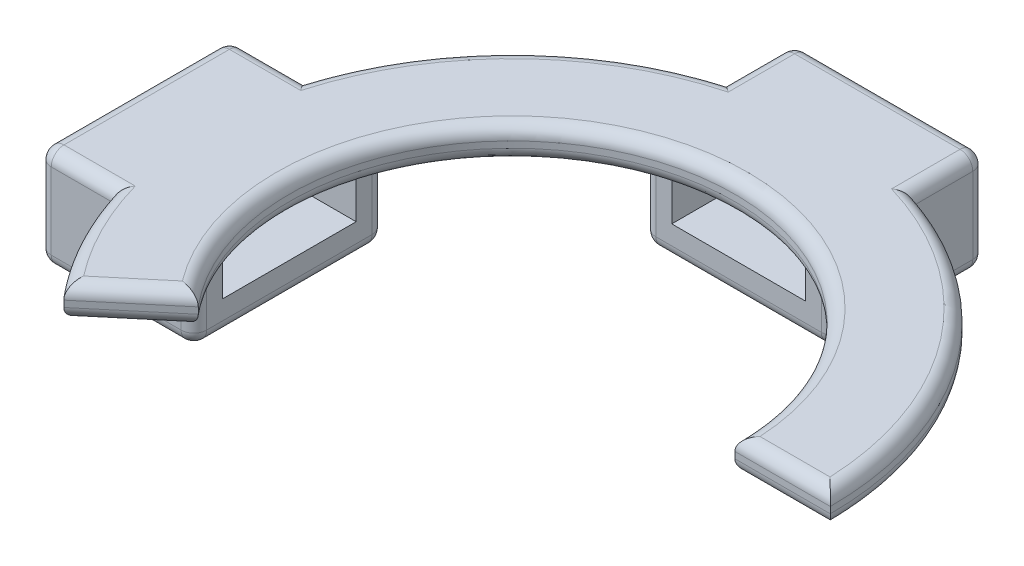
SolidWorks part; units mm, degrees
ref_plane "Front Plane" through (0, 0, 0) normal (0, 0, 1) x (1, 0, 0)
ref_plane "Top Plane" through (0, 0, 0) normal (0, 1, 0) x (1, 0, 0)
ref_plane "Right Plane" through (0, 0, 0) normal (1, 0, 0) x (0, 0, -1)
sketch "Sketch1" plane through (0, 0, 0) normal (0, 1, 0) x (1, 0, 0)
  line L0 (0, -32.004) -> (0, -22.9826) construction
  line L1 (0, 98.8258) -> (0, -27.4933) construction
  line L2 (-77.0851, 0) -> (82.0908, 0) construction
  line L5 (-15, 65) -> (15, 65)
  line L6 (-15, 65) -> (-15, 54.0833)
  line L7 (15, 65) -> (15, 53.7121)
  line L8 (-50.5901, 6.2047) -> (-35.5901, 6.2047)
  line L9 (34.4099, 6.2047) -> (49.4099, 6.2047)
  arc A2 (-50.5901, 6.2047) -> (49.4099, 6.2047) centre (-0.5901, 6.2047) cw
  arc A3 (-15, 54.0833) -> (15, 53.7121) centre (-0.5901, 6.2047) cw
  arc A4 (-35.5901, 6.2047) -> (34.4099, 6.2047) centre (-0.5901, 6.2047) cw
  dimension "D1" = 15
  dimension "D2" = 65
  dimension "D3" = 30
  dimension "D4" = 15
extrude "Boss-Extrude1" add sketch "Sketch1" along normal blind 5 contours L8 A4 L9 A2 | L6 A2 L7 L5 region at (0.0952, 0, -60.1952) region at (0.0147, 0, -55.0829)
sketch "Sketch2" plane through (0, 0, 0) normal (0, 1, 0) x (1, 0, 0)
  line L0 (-38.8923, -25.9347) -> (-27.4017, -16.2928)
  line L1 (-50.5901, 6.2047) -> (-35.5901, 6.2047)
  arc A0 (-35.5901, 6.2047) -> (-27.4017, -16.2928) centre (-0.5901, 6.2047) ccw
  arc A1 (-50.5901, 6.2047) -> (-38.8923, -25.9347) centre (-0.5901, 6.2047) ccw
  dimension "D1" = 15
extrude "Boss-Extrude2" add sketch "Sketch2" along normal blind 5
sketch "Sketch3" plane through (0, 0, 0) normal (0, 1, 0) x (1, 0, 0)
  line L0 (49.4099, 6.2047) -> (-70.2479, 6.2047) construction
  line L2 (-60, 21.2047) -> (-38.6351, 21.2047)
  line L3 (-60, 21.2047) -> (-60, -8.7953)
  line L4 (-60, -8.7953) -> (-38.6351, -8.7953)
  line L5 (-38.6351, 21.2047) -> (-38.6351, -8.7953)
  line L6 (0, -19.471) -> (0, 25.9779) construction
  dimension "D1" = 30
  dimension "D2" = 15
  dimension "D3" = 60
extrude "Boss-Extrude3" add sketch "Sketch3" along normal blind 5
sketch "Sketch4" plane through (0, 5, 0) normal (0, 1, 0) x (1, 0, 0)
  line L1 (-15, 65) -> (-10.5, 65)
  line L2 (-15, 65) -> (-15, 41.2047)
  line L3 (-15, 41.2047) -> (-10.5, 41.2047)
  line L4 (-10.5, 65) -> (-10.5, 41.2047)
  line L5 (15, 65) -> (10.5, 65)
  line L6 (15, 65) -> (15, 41.2047)
  line L7 (15, 41.2047) -> (10.5, 41.2047)
  line L8 (10.5, 65) -> (10.5, 41.2047)
  line L9 (-60, 21.2047) -> (-35.5901, 21.2047)
  line L10 (-60, 21.2047) -> (-60, 16.7047)
  line L11 (-60, 16.7047) -> (-35.5901, 16.7047)
  line L12 (-35.5901, 21.2047) -> (-35.5901, 16.7047)
  line L13 (-60, -8.7953) -> (-35.5901, -8.7953)
  line L14 (-60, -8.7953) -> (-60, -4.2953)
  line L15 (-60, -4.2953) -> (-35.5901, -4.2953)
  line L16 (-35.5901, -8.7953) -> (-35.5901, -4.2953)
  dimension "D1" = 4.5
  dimension "D2" = 4.5
  dimension "D3" = 4.5
  dimension "D4" = 4.5
extrude "Boss-Extrude4" add sketch "Sketch4" against normal blind 11
sketch "Sketch5" plane through (0, -6, 0) normal (0, -1, 0) x (-1, 0, 0)
  line L1 (15, 65) -> (-15, 65)
  line L2 (15, 65) -> (15, 41.2047)
  line L3 (15, 41.2047) -> (-15, 41.2047)
  line L4 (-15, 65) -> (-15, 41.2047)
  line L5 (60, 21.2047) -> (35.5901, 21.2047)
  line L6 (60, 21.2047) -> (60, -8.7953)
  line L7 (60, -8.7953) -> (35.5901, -8.7953)
  line L8 (35.5901, 21.2047) -> (35.5901, -8.7953)
extrude "Boss-Extrude5" add sketch "Sketch5" along normal blind 5
fillet "Fillet1" radius 2 34 edges at (15, -5.5, -41.2047) (-15, -5.5, -41.2047) (-35.5901, -5.5, -21.2047) (0, -11, -41.2047) (0, -11, -65) (-15, -11, -53.1024) (15, -11, -53.1024) (15, -3, -65) (0, 5, -65) (-15, -3, -65) (-15, 5, -59.5416) (15, 5, -59.356) (-44.4354, 5, 17.8285) (-44.4354, 0, 17.8285) (41.9099, 5, -6.2047) (41.9099, 0, -6.2047) (-12.5608, 5, -39.094) (-12.5608, 0, -39.094) (-33.147, 5, 21.1138) (-33.147, 0, 21.1138) (-35.5901, -11, -6.2047) (-54.1435, 5, 8.7953) (-35.5901, -5.5, 8.7953) (-47.7951, -11, 8.7953) (-47.7951, -11, -21.2047) (-54.1435, 5, -21.2047) (-35.7265, 0, -41.7777) (39.9037, 0, -35.5347) (39.9037, 5, -35.5347) (-35.7265, 5, -41.7777) (-60, -11, -6.2047) (-60, -3, -21.2047) (-60, -3, 8.7953) (-60, 5, -6.2047)
